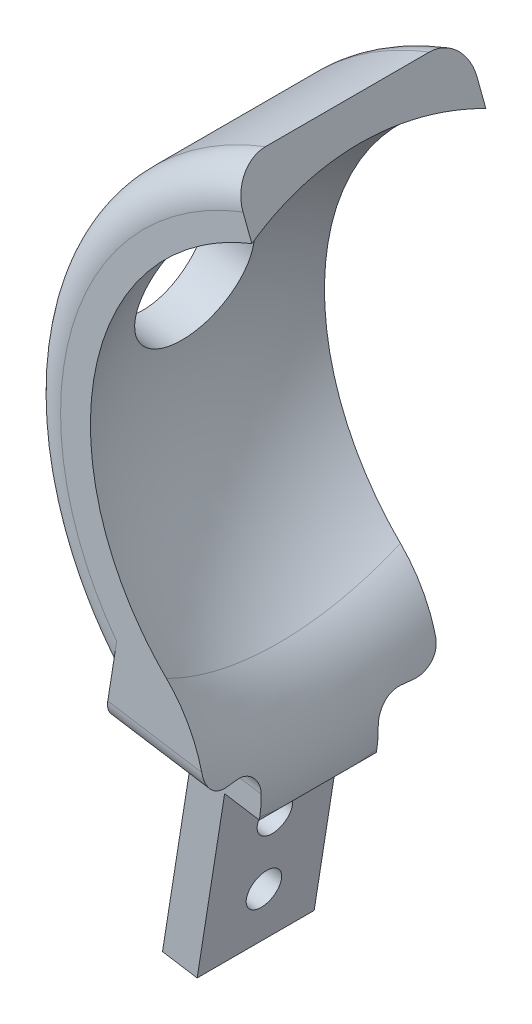
SolidWorks part; units mm, degrees
note: '?' marks a value the reader was unsure of.
material "聚脂树脂"
ref_plane "前视基准面" through (0, 0, 0) normal (0, 0, 1) x (1, 0, 0)
ref_plane "上视基准面" through (0, 0, 0) normal (0, 1, 0) x (1, 0, 0)
ref_plane "右视基准面" through (0, 0, 0) normal (1, 0, 0) x (0, 0, -1)
other "Configuration Table"
sketch "草图1" plane through (0, 0, 0) normal (0, 0, 1) x (1, 0, 0)
  circle A0 centre (0, 0) radius 13.75
extrude "凸台-拉伸1" add sketch "草图1" along normal blind 10
ref_axis "基准轴1" through (0, 0, -1.5) along (0, 0, 1)?
sketch "草图2" plane through (0, 0, 0) normal (0, 0, 1) x (1, 0, 0)
  line L0 (0, 0) -> (0, 13.75) construction
  circle A0 centre (0, 0) radius 13.75 construction
  arc A1 (0.2416, 10.9348) -> (-0.2416, 10.9348) centre (0, 0) ccw
  arc A2 (3.9764, 15.6228) -> (-3.9764, 15.6228) centre (0, 0) ccw
  spline S0 degree 3 poles (0.2416, 10.9348) (0.764, 11.1168) (0.6964, 11.4839) (0.7661, 11.8375) (0.7736, 11.8719) (0.7829, 11.9108) (0.7941, 11.954) (0.8075, 12.0015) (0.8231, 12.0532) (0.8413, 12.1091) (0.8621, 12.169) (0.8857, 12.2329) (0.9123, 12.3007) (0.9421, 12.3723) (0.9752, 12.4476) (1.0117, 12.5264) (1.0519, 12.6088) (1.0959, 12.6945) (1.1438, 12.7834) (1.1957, 12.8755) (1.2519, 12.9705) (1.3125, 13.0684) (1.3775, 13.1691) (1.4472, 13.2723) (1.5216, 13.3779) (1.601, 13.4858) (1.6853, 13.5958) (1.7747, 13.7078) (1.8694, 13.8216) (1.9693, 13.937) (2.0748, 14.0539) (2.1857, 14.1721) (2.3023, 14.2914) (2.4246, 14.4116) (2.5527, 14.5326) (2.6866, 14.6542) (2.8265, 14.7761) (2.9725, 14.8983) (3.1245, 15.0204) (3.2826, 15.1424) (3.4469, 15.2639) (3.6768, 15.427) (3.8549, 15.5454) (3.9764, 15.6228) knots 0 0 0 0 0.165916 0.170906 0.176664 0.183189 0.190482 0.198542 0.207371 0.216967 0.22733 0.238462 0.250361 0.263027 0.276462 0.290664 0.305634 0.321371 0.337876 0.355149 0.37319 0.391998 0.411574 0.431917 0.453028 0.474907 0.497554 0.520968 0.54515 0.570099 0.595817 0.622302 0.649554 0.677575 0.706363 0.735918 0.766242 0.797333 0.829191 0.861818 0.895212 0.929373 1 1 1 1
  spline S1 degree 3 poles (-0.2416, 10.9348) (-0.764, 11.1168) (-0.6964, 11.4839) (-0.7661, 11.8375) (-0.7736, 11.8719) (-0.7829, 11.9108) (-0.7941, 11.954) (-0.8075, 12.0015) (-0.8231, 12.0532) (-0.8413, 12.1091) (-0.8621, 12.169) (-0.8857, 12.2329) (-0.9123, 12.3007) (-0.9421, 12.3723) (-0.9752, 12.4476) (-1.0117, 12.5264) (-1.0519, 12.6088) (-1.0959, 12.6945) (-1.1438, 12.7834) (-1.1957, 12.8755) (-1.2519, 12.9705) (-1.3125, 13.0684) (-1.3775, 13.1691) (-1.4472, 13.2723) (-1.5216, 13.3779) (-1.601, 13.4858) (-1.6853, 13.5958) (-1.7747, 13.7078) (-1.8694, 13.8216) (-1.9693, 13.937) (-2.0748, 14.0539) (-2.1857, 14.1721) (-2.3023, 14.2914) (-2.4246, 14.4116) (-2.5527, 14.5326) (-2.6866, 14.6542) (-2.8265, 14.7761) (-2.9725, 14.8983) (-3.1245, 15.0204) (-3.2826, 15.1424) (-3.4469, 15.2639) (-3.6768, 15.427) (-3.8549, 15.5454) (-3.9764, 15.6228) knots 0 0 0 0 0.165916 0.170906 0.176664 0.183189 0.190482 0.198542 0.207371 0.216967 0.22733 0.238462 0.250361 0.263027 0.276462 0.290664 0.305634 0.321371 0.337876 0.355149 0.37319 0.391998 0.411574 0.431917 0.453028 0.474907 0.497554 0.520968 0.54515 0.570099 0.595817 0.622302 0.649554 0.677575 0.706363 0.735918 0.766242 0.797333 0.829191 0.861818 0.895212 0.929373 1 1 1 1
extrude "切除-拉伸1" cut sketch "草图2" along normal through all
pattern_circular "阵列(圆周)1" count 20 every 18 about axis through (0, 0, -1.5) along (0, 0, 1) of "切除-拉伸1"
sketch "草图3" plane through (0, 0, 0) normal (0, 0, 1) x (1, 0, 0)
  circle A0 centre (0, 0) radius 12.5 construction
  dimension "Dn" = 25
sketch "草图6" plane through (0, 0, 0) normal (0, 0, -1) x (-1, 0, 0)
  line L0 (0, 0) -> (-10.311, 65.1009) construction
  line L1 (0, 0) -> (38.9643, 6.1713) construction
  line L2 (0, 0) -> (-30.4582, -4.8241) construction
  line L3 (-12.3461, -1.9554) -> (-21.1812, 53.827) construction
  line L4 (4.4446, 0.704) -> (-1.1233, 35.8583)
  line L5 (-4.4446, -0.704) -> (-10.0125, 34.4504)
  line L6 (-10.0125, 34.4504) -> (-15.7198, 70.4851)
  line L7 (-15.7198, 70.4851) -> (-21.4537, 55.5478) construction
  line L8 (-15.7198, 70.4851) -> (-7.9754, 90.6601) construction
  line L9 (-15.7198, 70.4851) -> (-11.3112, 81.9699)
  line L10 (-4.4446, -0.704) -> (4.4446, 0.704)
  circle A0 centre (0, 0) radius 12.5 construction
  circle A1 centre (-21.4537, 55.5478) radius 24 construction
  circle A2 centre (-21.4537, 55.5478) radius 28.3019 construction
  arc A3 (-11.3112, 81.9699) -> (-1.1233, 35.8583) centre (-21.4537, 55.5478) cw
  dimension "D1" = 25
  dimension "D4" = 48
  dimension "D5" = 30
  dimension "D2" = 9
  dimension "D3" = 58.22
extrude "凸台-拉伸2" add sketch "草图6" against normal blind 15 and the other way blind 5
sketch "草图7" plane through (4.4446, -0.704, 0) normal (0.9877, -0.1564, 0) x (0, 0, -1)
  line L0 (0, 0) -> (0, 34)
  line L1 (0, 34) -> (5, 34)
  line L2 (5, 0) -> (5, 72.0764) construction
  line L3 (5, 34) -> (5, 0)
  line L4 (5, 0) -> (0, 0) construction
  line L5 (5, 0) -> (5, 72.0764) construction
  line L6 (5, 0) -> (0, 0)
  line L7 (-5, 4.6588) -> (-5, 27.3083) construction
  line L8 (-10, 4.6588) -> (0, 4.6588) construction
  line L9 (-15, 34) -> (-15, 0)
  line L10 (-10, 34) -> (-15, 34)
  line L11 (-10, 0) -> (-10, 34)
  line L12 (-15, 0) -> (-10, 0)
  dimension "D1" = 34
extrude "切除-拉伸3" cut sketch "草图7" against normal blind 32 and the other way blind 10
ref_plane "基准面1" through (12.5, 0, 0) normal (1, 0, 0) x (0, 0, -1)
ref_axis "基准轴2" through (0, 0, -6) along (0, 0, 1)?
ref_plane "基准面2" through (0, 0, 0) normal (-0.9877, 0.1564, 0) x (0, 0, 1)
ref_plane "基准面3" through (12.3461, -1.9554, 0) normal (-0.9877, 0.1564, 0) x (0, 0, 1)
sketch "草图13" plane through (12.3461, -1.9554, 0) normal (-0.9877, 0.1564, 0) x (0, 0, 1)
  line L0 (5, 0.4331) -> (5, 90.5431) construction
  line L1 (0, 0.4331) -> (10, 0.4331) construction
  line L2 (5, 82.6531) -> (5, 34.6531)
  arc A0 (5, 82.6531) -> (5, 34.6531) centre (5, 58.6531) cw
  dimension "D1" = 24
  dimension "D2" = 58.22
revolve "切除-旋转2" cut sketch "草图13" angle 360 about L0
sketch "草图12" plane through (0, 0, -5) normal (0, 0, -1) x (-1, 0, 0)
  line L0 (0, 0) -> (-14.3434, 90.5607) construction
  line L1 (-12.3461, -1.9554) -> (-26.4984, 87.3984) construction
  line L2 (-11.6703, 81.0345) -> (-11.3112, 81.9699)
  line L3 (0, 0) -> (-28.4747, -4.5099) construction
  line L4 (-1.1233, 35.8583) -> (-1.3214, 37.1092)
  line L5 (-0.8742, 34.2854) -> (-1.1233, 35.8583) construction
  line L6 (-13.501, 76.2653) -> (-11.3112, 81.9699) construction
  circle A0 centre (-21.4537, 55.5478) radius 28.3019
  circle A1 centre (-21.4537, 55.5478) radius 27.3
  dimension "D3" = 54.6
  dimension "D4" = 56.6039
  dimension "D1" = 12.5
  dimension "D2" = 58.22
extrude "切除-拉伸4" cut sketch "草图12" against normal blind 22
fillet "圆角2" radius 2 4 edges at (5.3188, 33.5814, 10) (5.3188, 33.5814, 15) (5.3188, 33.5814, 0) (5.3188, 33.5814, -5)
fillet "圆角3" radius 3 2 edges at (-5.1188, 61.8083, 15) (-5.1188, 61.8083, -5)
sketch "草图16" plane through (0, 0, 10) normal (0, 0, 1) x (1, 0, 0)
  circle A0 centre (0, 0) radius 2
  dimension "D1" = 4
extrude "切除-拉伸5" cut sketch "草图16" against normal blind 16.5
sketch "草图18" plane through (0, 0, 10) normal (0, 0, 1) x (1, 0, 0)
  circle A0 centre (0, 0) radius 5
  circle A1 centre (0, 0) radius 2
  dimension "D1" = 10
  dimension "D2" = 4
extrude "凸台-拉伸4" add sketch "草图18" along normal blind 3.5
sketch "草图19" plane through (0, 0, 0) normal (0, 0, -1) x (-1, 0, 0)
  circle A0 centre (0, 0) radius 8
  dimension "D1" = 16
extrude "切除-拉伸7" cut sketch "草图19" against normal blind 3
fillet "圆角4" radius 2 1 edges at (5, 0, 10)
sketch "草图20" plane through (0, 0, 0) normal (0, 0, -1) x (-1, 0, 0)
  line L0 (0, 0) -> (3.6089, 10.325)
  line L1 (3.6089, 10.325) -> (7.1451, 20.4421)
  line L2 (0, 0) -> (10.9348, -0.2416)
  line L3 (10.9348, -0.2416) -> (20.7519, -0.2416)
  circle A0 centre (0, 0) radius 17.5
  circle A1 centre (0, 0) radius 10.9375
  arc A2 (-8.7044, 6.6228) -> (-8.9885, 6.2318) centre (0, 0) ccw construction
  dimension "D1" = 35
extrude "切除-拉伸8" cut sketch "草图20" against normal blind 10 contours A1 L3 A0 L1
sketch "草图21" plane through (0, 0, 0) normal (0, 0, -1) x (-1, 0, 0)
  line L0 (0, 0) -> (0, 81.9556) construction
  line L1 (0, 0) -> (-12.0239, 75.9161) construction
  line L2 (0, 0) -> (48.924, 7.7488) construction
  line L3 (-3.828, 14.5807) -> (-0.865, 15.05)
  line L4 (-0.865, 15.05) -> (-3.2115, 29.8653)
  line L5 (-3.2115, 29.8653) -> (16.5423, 32.994)
  line L6 (16.5423, 32.994) -> (24.364, -16.3904)
  line L7 (24.364, -16.3904) -> (3.0899, -19.7599)
  line L8 (-18.1066, -23.1171) -> (3.0899, -19.7599)
  line L9 (-25.9283, 26.2673) -> (-18.1066, -23.1171)
  line L10 (-6.1746, 29.396) -> (-25.9283, 26.2673)
  line L11 (-3.828, 14.5807) -> (-6.1746, 29.396)
  point P3 (2.8668, -20.6752)
  point P16 (-2.3465, 14.8153)
  dimension "D1" = 9
  dimension "D2" = 1.5
  dimension "D3" = 15
  dimension "D4" = 15
  dimension "D5" = 20
  dimension "D6" = 50
extrude "切除-拉伸9" cut sketch "草图21" against normal blind 22
sketch "草图22" plane through (1.4815, -0.2347, 0) normal (0.9877, -0.1564, 0) x (0, 0, -1)
  line L0 (-5, 15) -> (-5, 85.593) construction
  line L1 (-10, 15) -> (0, 15) construction
  line L2 (-10, 30) -> (0, 30) construction
  circle A0 centre (-5, 25.5) radius 1.5
  circle A1 centre (-5, 19.5) radius 1.5
  dimension "D1" = 3
  dimension "D2" = 3
  dimension "D3" = 6
  dimension "D4" = 4.5
extrude "切除-拉伸10" cut sketch "草图22" against normal blind 22
sketch "草图24" plane through (0, 0, 0) normal (-0.9877, 0.1564, 0) x (0, 0, 1)
  line L0 (-5, 60.0605) -> (15, 60.0605) construction
  line L1 (-5, 79.2644) -> (-5, 40.8565) construction
  line L2 (15, 40.8565) -> (15, 79.2644) construction
  line L3 (5, 36.8591) -> (5, 81.8625) construction
  line L4 (12, 36.8591) -> (-2, 36.8591) construction
  line L5 (-2, 81.8625) -> (12, 81.8625) construction
  circle A0 centre (5, 60.0605) radius 5
  dimension "D1" = 10
extrude "切除-拉伸11" cut sketch "草图24" along normal blind 26
fillet "圆角5" radius 10 1 edges at (10.0803, 34.8782, 5)
